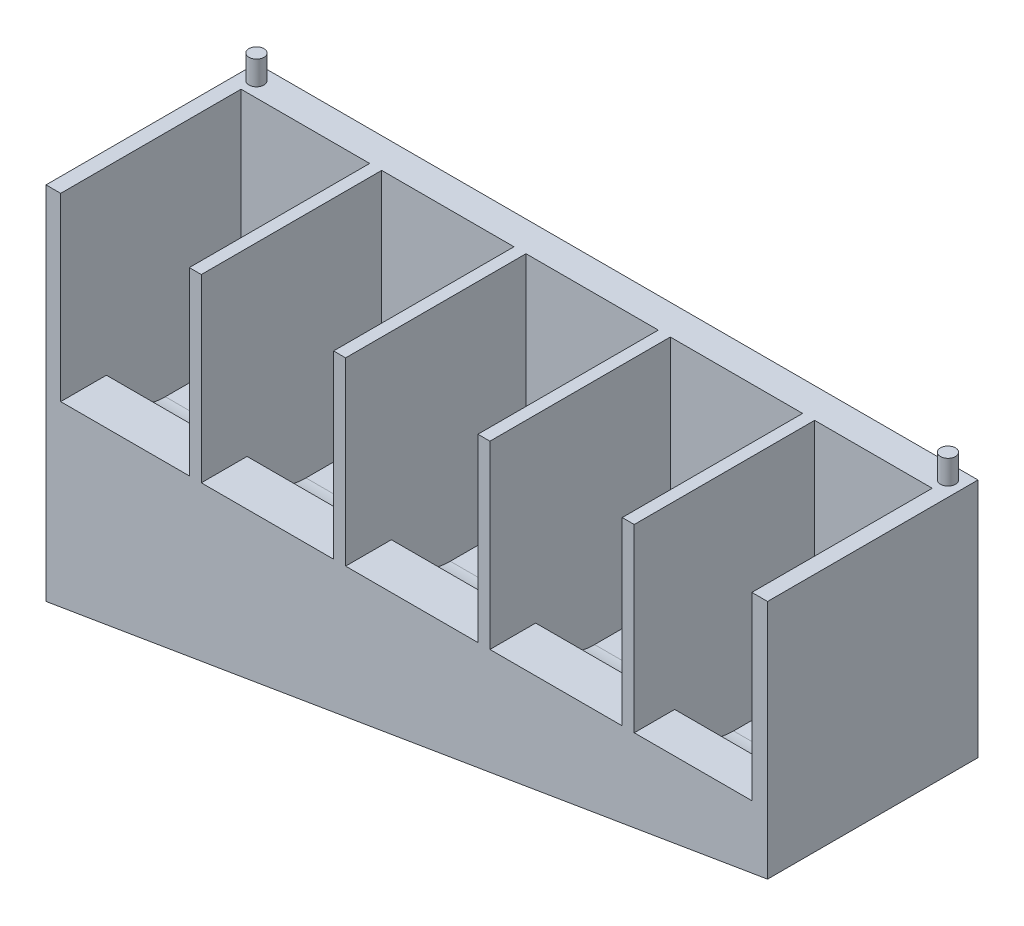
SolidWorks part; units mm, degrees
ref_plane "Front Plane" through (0, 0, 0) normal (0, 0, 1) x (1, 0, 0)
ref_plane "Top Plane" through (0, 0, 0) normal (0, 1, 0) x (1, 0, 0)
ref_plane "Right Plane" through (0, 0, 0) normal (1, 0, 0) x (0, 0, -1)
sketch "Sketch1" plane through (0, 0, 0) normal (0, 1, 0) x (1, 0, 0)
  line L1 (-41.3396, -6.5377) -> (78.6604, -6.5377)
  line L2 (-41.3396, -6.5377) -> (-41.3396, 28.4623)
  line L3 (-41.3396, 28.4623) -> (78.6604, 28.4623)
  line L4 (78.6604, -6.5377) -> (78.6604, 28.4623)
  dimension "D1" = 35
  dimension "D2" = 120
extrude "Boss-Extrude1" add sketch "Sketch1" along normal blind 40
sketch "Sketch2" plane through (0, 40, 0) normal (0, 1, 0) x (1, 0, 0)
  line L0 (-41.3396, -6.5377) -> (78.6604, -6.5377) construction
  line L1 (-38.8996, -6.5377) -> (-17.5096, -6.5377)
  line L2 (-38.8996, -6.5377) -> (-38.8996, 23.4623)
  line L3 (-38.8996, 23.4623) -> (-17.5096, 23.4623)
  line L4 (-17.5096, -6.5377) -> (-17.5096, 23.4623)
  line L6 (-41.3396, 28.4623) -> (-41.3396, -6.5377) construction
  line L8 (-15.5096, 23.4623) -> (6.4904, 23.4623)
  line L9 (-15.5096, 23.4623) -> (-15.5096, -6.5377)
  line L10 (-15.5096, -6.5377) -> (6.4904, -6.5377)
  line L11 (6.4904, 23.4623) -> (6.4904, -6.5377)
  line L12 (8.4904, -6.5377) -> (30.4904, -6.5377)
  line L13 (8.4904, -6.5377) -> (8.4904, 23.4623)
  line L14 (8.4904, 23.4623) -> (30.4904, 23.4623)
  line L15 (30.4904, -6.5377) -> (30.4904, 23.4623)
  line L16 (32.4904, -6.5377) -> (54.4904, -6.5377)
  line L17 (32.4904, -6.5377) -> (32.4904, 23.4623)
  line L18 (32.4904, 23.4623) -> (54.4904, 23.4623)
  line L19 (54.4904, -6.5377) -> (54.4904, 23.4623)
  line L20 (56.4904, 23.4623) -> (76.0504, 23.4623)
  line L21 (56.4904, 23.4623) -> (56.4904, -6.5377)
  line L22 (56.4904, -6.5377) -> (76.0504, -6.5377)
  line L23 (76.0504, 23.4623) -> (76.0504, -6.5377)
  dimension "D1" = 21.39
  dimension "D2" = 2.44
  dimension "D3" = 22
  dimension "D4" = 2
  dimension "D5" = 22
  dimension "D6" = 22
  dimension "D7" = 2
  dimension "D8" = 2
  dimension "D9" = 30
  dimension "D10" = 19.56
  dimension "D11" = 2
  dimension "D12" = 30
extrude "Cut-Extrude1" cut sketch "Sketch2" against normal blind 30
sketch "Sketch3" plane through (0, 10, 0) normal (0, 1, 0) x (1, 0, 0)
  line L0 (-17.5096, -6.5377) -> (-17.5096, 23.4623) construction
  line L1 (-38.8996, 23.4623) -> (-17.5096, 23.4623)
  line L2 (-38.8996, 23.4623) -> (-38.8996, 1.0697)
  line L3 (-38.8996, 1.0697) -> (-17.5096, 1.0697)
  line L4 (-17.5096, 23.4623) -> (-17.5096, 1.0697)
  line L5 (6.4904, -6.5377) -> (6.4904, 23.4623) construction
  line L6 (-15.5096, 23.4623) -> (6.4904, 23.4623)
  line L7 (-15.5096, 23.4623) -> (-15.5096, 1.0697)
  line L8 (-15.5096, 1.0697) -> (6.4904, 1.0697)
  line L9 (6.4904, 23.4623) -> (6.4904, 1.0697)
  line L10 (30.4904, -6.5377) -> (30.4904, 23.4623) construction
  line L11 (8.4904, 23.4623) -> (30.4904, 23.4623)
  line L12 (8.4904, 23.4623) -> (8.4904, 1.0697)
  line L13 (8.4904, 1.0697) -> (30.4904, 1.0697)
  line L14 (30.4904, 23.4623) -> (30.4904, 1.0697)
  line L15 (54.4904, -6.5377) -> (54.4904, 23.4623) construction
  line L16 (32.4904, 23.4623) -> (54.4904, 23.4623)
  line L17 (32.4904, 23.4623) -> (32.4904, 1.0697)
  line L18 (32.4904, 1.0697) -> (54.4904, 1.0697)
  line L19 (54.4904, 23.4623) -> (54.4904, 1.0697)
  line L20 (76.0504, -6.5377) -> (76.0504, 23.4623) construction
  line L21 (56.4904, 23.4623) -> (76.0504, 23.4623)
  line L22 (56.4904, 23.4623) -> (56.4904, 0.1857)
  line L23 (56.4904, 0.1857) -> (76.0504, 0.1857)
  line L24 (76.0504, 23.4623) -> (76.0504, 0.1857)
  dimension "D1" = 23.2766
extrude "Cut-Extrude2" cut sketch "Sketch3" against normal blind 8
fillet "Fillet1" radius 10 5 edges at (66.2704, 2, -0.1857) (43.4904, 2, -1.0697) (19.4904, 2, -1.0697) (-28.2046, 2, -1.0697) (-4.5096, 2, -1.0697)
sketch "Sketch4" plane through (0, 40, 0) normal (0, 1, 0) x (1, 0, 0)
  line L0 (78.6604, 28.4623) -> (-41.3396, 28.4623) construction
  line L1 (-41.3396, 28.4623) -> (-41.3396, -6.5377) construction
  line L2 (78.6604, -6.5377) -> (78.6604, 28.4623) construction
  circle A0 centre (-38.8396, 25.9623) radius 1.25
  circle A1 centre (76.1604, 25.9623) radius 1.25
  dimension "D1" = 2.5
  dimension "D2" = 2.5
  dimension "D3" = 2.5
  dimension "D5" = 2.5
  dimension "D6" = 2.5
  dimension "D4" = 2.5
extrude "Boss-Extrude2" add sketch "Sketch4" along normal blind 4
sketch "Sketch5" plane through (0, 0, 6.5377) normal (0, 0, 1) x (1, 0, 0)
  line L0 (-41.3396, 0) -> (-41.3396, -20)
  line L1 (-41.3396, -20) -> (78.6604, 0)
  line L2 (78.6604, 0) -> (-41.3396, 0)
  dimension "D1" = 20
extrude "Boss-Extrude3" add sketch "Sketch5" against normal blind 35
